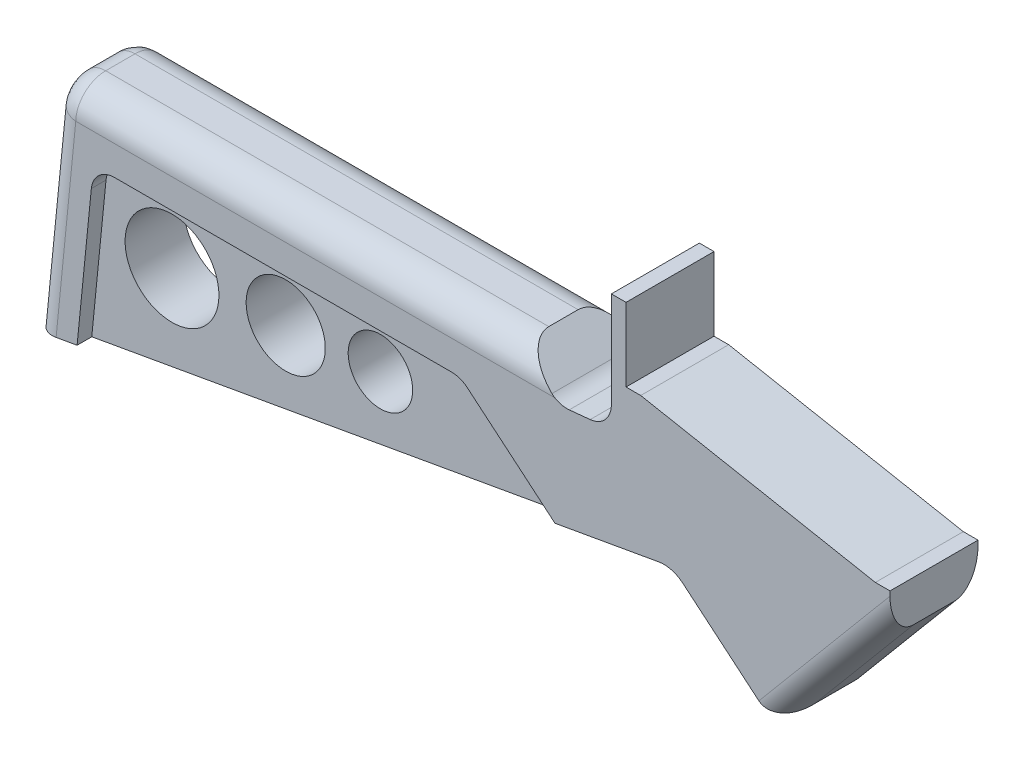
SolidWorks part; units mm, degrees
ref_plane "Front Plane" through (0, 0, 0) normal (0, 0, 1) x (1, 0, 0)
ref_plane "Top Plane" through (0, 0, 0) normal (0, 1, 0) x (1, 0, 0)
ref_plane "Right Plane" through (0, 0, 0) normal (1, 0, 0) x (0, 0, -1)
sketch "Sketch1" plane through (0, 0, 0) normal (0, 0, 1) x (1, 0, 0)
  line L0 (0, 0) -> (85, 0) construction
  line L1 (0, 0) -> (0, 14) construction
  line L2 (0, 14) -> (85, 14) construction
  line L3 (85, 14) -> (85, 0)
  line L4 (80, 14) -> (0, 29.1972)
  line L5 (0, 29.1972) -> (-5, 29.1972)
  line L6 (-5, 29.1972) -> (-5, 54.1972)
  line L7 (-5, 54.1972) -> (-10, 54.1972)
  line L8 (-10, 54.1972) -> (-10, 14.1972)
  line L9 (85, 0) -> (46.4327, -45.9627)
  line L10 (46.4327, -45.9627) -> (10.774, -16.0415)
  line L11 (10.774, -16.0415) -> (-207.4926, -54.7717)
  line L12 (-207.4926, -54.7717) -> (-199.651, 23.8735)
  line L15 (80, 14) -> (85, 14)
  line L16 (-199.651, 23.8735) -> (-41.3345, 23.8735)
  line L17 (-41.3345, 23.8735) -> (-27.713, 12.4437)
  line L18 (-27.713, 12.4437) -> (-10, 14.1972)
  point P16 (0, 0)
  point P17 (-41.3345, 23.7563)
  dimension "D1" = 85
  dimension "D2" = 14
  dimension "D3" = 5
  dimension "D4" = 5
  dimension "D5" = 10.756
  dimension "D6" = 50
  dimension "D7" = 60
  dimension "D8" = 5
  dimension "D9" = 80
  dimension "D10" = 40
  dimension "D11" = 25
extrude "Boss-Extrude1" add sketch "Sketch1" along normal blind 15 contours L3 L9 L10 L11 L12 L16 L17 L18 L8 L7 L6 L5 L4 L15
sketch "Sketch2" plane through (0, 0, 0) normal (0, 0, 1) x (1, 0, 0)
  line L0 (10.774, -16.0415) -> (-29.226, -23.1392) construction
  line L1 (10.774, -16.0415) -> (-207.4926, -54.7717) construction
  line L2 (-29.226, -23.1392) -> (-61.4185, 3.8735)
  line L3 (-61.4185, 3.8735) -> (-186.5708, 3.8735)
  line L4 (-186.5708, 3.8735) -> (-192.1467, -52.0487)
  line L5 (-207.4926, -54.7717) -> (-199.651, 23.8735) construction
  line L6 (-199.651, 23.8735) -> (-41.3345, 23.8735) construction
  line L7 (-41.3345, 23.8735) -> (-27.713, 12.4437) construction
  line L8 (-192.1467, -52.0487) -> (-29.226, -23.1392)
  dimension "D1" = 40
  dimension "D2" = 15
  dimension "D3" = 20
extrude "Cut-Extrude1" cut sketch "Sketch2" along normal blind 5
fillet "Fillet1" radius 10 2 edges at (-120.4927, 23.8735, 0) (10.774, -16.0415, 7.5)
fillet "Fillet2" radius 8 9 edges at (-199.651, 23.8735, 12.5) (-199.943, 20.9445, 2.9289) (-204.0703, -20.4491, 0) (65.7164, -22.9813, 0) (46.4327, -45.9627, 7.5) (-186.5708, 3.8735, 2.5) (-61.4185, 3.8735, 2.5) (-10, 14.1972, 7.5) (-27.713, 12.4437, 7.5)
sketch "Sketch3" plane through (0, 0, 5) normal (0, 0, -1) x (-1, 0, 0)
  line L0 (73.9846, -2.1265) -> (179.1682, -2.1265) construction
  line L1 (64.3302, 3.8735) -> (179.3288, 3.8735) construction
  line L2 (64.3302, 3.8735) -> (179.3288, 3.8735) construction
  circle A0 centre (93.7405, -13.1265) radius 11
  circle A1 centre (164.801, -18.1265) radius 16
  circle A2 centre (126.0265, -15.6265) radius 13.5
  dimension "D2" = 22
  dimension "D3" = 32
  dimension "D4" = 27
  dimension "D1" = 6
extrude "Cut-Extrude2" cut sketch "Sketch3" against normal through all
mirror "Mirror1" about plane through (0, 0, 15) normal (0, 0, -1) of bodies 104 102
